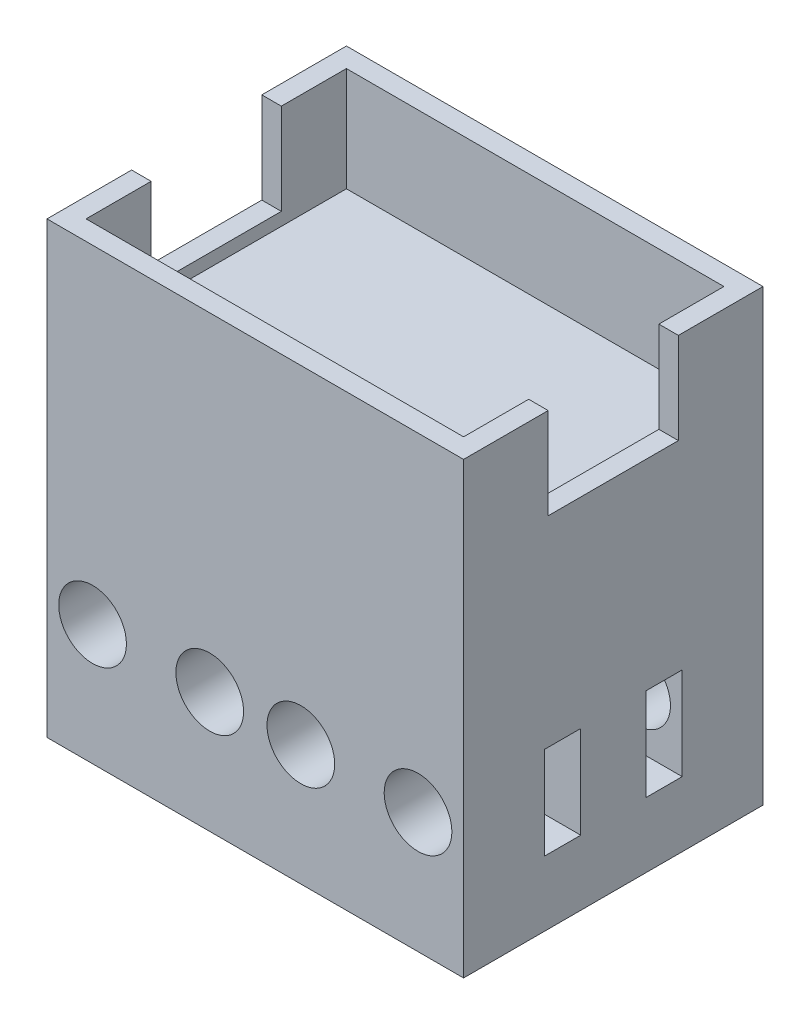
SolidWorks part; units mm, degrees
ref_plane "Front Plane" through (0, 0, 0) normal (0, 0, 1) x (1, 0, 0)
ref_plane "Top Plane" through (0, 0, 0) normal (0, 1, 0) x (1, 0, 0)
ref_plane "Right Plane" through (0, 0, 0) normal (1, 0, 0) x (0, 0, -1)
sketch "Sketch4" plane through (0, 0, 0) normal (0, 1, 0) x (1, 0, 0)
  line L1 (-16, -11.5) -> (16, -11.5)
  line L2 (-16, -11.5) -> (-16, 11.5)
  line L3 (-16, 11.5) -> (16, 11.5)
  line L4 (16, -11.5) -> (16, 11.5)
  line L5 (-16, -11.5) -> (16, 11.5) construction
  line L6 (-16, 11.5) -> (16, -11.5) construction
  point P0 (0, 0)
  dimension "D1" = 32
  dimension "D2" = 23
extrude "Boss-Extrude3" add sketch "Sketch4" along normal blind 19.5
sketch "Sketch5" plane through (0, 19.5, 0) normal (0, 1, 0) x (1, 0, 0)
  line L1 (-14.5, -10) -> (14.5, -10)
  line L2 (-14.5, -10) -> (-14.5, 10)
  line L3 (-14.5, 10) -> (14.5, 10)
  line L4 (14.5, -10) -> (14.5, 10)
  line L5 (-14.5, -10) -> (14.5, 10) construction
  line L6 (-14.5, 10) -> (14.5, -10) construction
  point P0 (0, 0)
  dimension "D1" = 29
  dimension "D2" = 20
extrude "Cut-Extrude2" cut sketch "Sketch5" against normal blind 8
sketch "Sketch7" plane through (16, 0, 0) normal (1, 0, 0) x (0, 0, -1)
  line L1 (-5, 12.5) -> (5, 12.5)
  line L2 (-5, 12.5) -> (-5, 19.5)
  line L3 (-5, 19.5) -> (5, 19.5)
  line L4 (5, 12.5) -> (5, 19.5)
  line L5 (-11.5, 19.5) -> (11.5, 19.5) construction
  point P6 (0, 19.5)
  point P8 (0, 19.5)
  dimension "D1" = 10
  dimension "D2" = 7
extrude "Cut-Extrude4" cut sketch "Sketch7" against normal through all
sketch "Sketch8" plane through (0, 0, 0) normal (0, -1, 0) x (-1, 0, 0)
  line L17 (-16, -11.5) -> (16, -11.5)
  line L18 (-16, -11.5) -> (-16, 11.5)
  line L19 (-16, 11.5) -> (16, 11.5)
  line L20 (16, -11.5) -> (16, 11.5)
  line L21 (-16, -11.5) -> (16, 11.5) construction
  line L22 (-16, 11.5) -> (16, -11.5) construction
  point P4 (0, 0)
extrude "Boss-Extrude4" add sketch "Sketch8" along normal blind 10
ref_plane "Plane1" through (0, 0, 0) normal (0, 0, -1) x (-1, 0, 0)
sketch "Sketch12" plane through (0, 0, -11.5) normal (0, 0, -1) x (-1, 0, 0)
  line L0 (0, 19.5) -> (0, -10) construction
  line L1 (-16, 19.5) -> (16, 19.5) construction
  line L2 (16, -10) -> (-16, -10) construction
  line L3 (-16, 19.5) -> (0, -10) construction
  line L4 (0, 19.5) -> (-16, -10) construction
  line L5 (-8, 4.75) -> (-8, -10) construction
  line L6 (-16, 19.5) -> (-16, -10) construction
  circle A0 centre (-12.5, -5.7269) radius 2.6
  circle A1 centre (-3.5, -5.7269) radius 2.6
  circle A2 centre (3.5, -5.7269) radius 2.6
  circle A3 centre (12.5, -5.7269) radius 2.6
  dimension "D1" = 5.2
  dimension "D3" = 3.5
  dimension "D2" = 4.2731
extrude "Cut-Extrude5" cut sketch "Sketch12" against normal blind 7
pattern_circular "CirPattern1" count 2 over 180 about axis through (0, 11.5, 0) along (0, 1, 0) of "Cut-Extrude5"
sketch "Sketch13" plane through (0, -10, 0) normal (0, -1, 0) x (-1, 0, 0)
  line L0 (16, -11.5) -> (16, 11.5) construction
  line L1 (16, 2.5) -> (1, 2.5)
  line L2 (16, 2.5) -> (16, 5.2916)
  line L3 (16, 5.2916) -> (1, 5.2916)
  line L4 (1, 2.5) -> (1, 5.2916)
  line L5 (16, 2.5) -> (1, 5.2916) construction
  line L6 (16, 5.2916) -> (1, 2.5) construction
  line L7 (13.475, 0) -> (-13.475, 0) construction
  line L8 (0, -11.5) -> (0, 11.5) construction
  line L9 (-16, -11.5) -> (16, -11.5) construction
  line L10 (16, 11.5) -> (-16, 11.5) construction
  line L11 (-16, 5.2916) -> (-1, 5.2916)
  line L12 (-1, 2.5) -> (-1, 5.2916)
  line L13 (-16, 2.5) -> (-1, 2.5)
  line L14 (-16, 2.5) -> (-16, 5.2916)
  line L15 (-16, -2.5) -> (-16, -5.2916)
  line L16 (-16, -2.5) -> (-1, -2.5)
  line L17 (-1, -2.5) -> (-1, -5.2916)
  line L18 (-16, -5.2916) -> (-1, -5.2916)
  line L19 (16, -5.2916) -> (1, -5.2916)
  line L20 (1, -2.5) -> (1, -5.2916)
  line L21 (16, -2.5) -> (1, -2.5)
  line L22 (16, -2.5) -> (16, -5.2916)
  point P4 (8.5, 3.8958)
  dimension "D1" = 15
  dimension "D2" = 2.7916
  dimension "D3" = 2.5
extrude "Cut-Extrude6" cut sketch "Sketch13" against normal blind 7.1
sketch "Sketch14" plane through (0, -10, 0) normal (0, -1, 0) x (-1, 0, 0)
  line L1 (16, 11.5) -> (-16, 11.5)
  line L2 (16, 11.5) -> (16, -11.5)
  line L3 (16, -11.5) -> (-16, -11.5)
  line L4 (-16, 11.5) -> (-16, -11.5)
  line L5 (16, 11.5) -> (-16, -11.5) construction
  line L6 (16, -11.5) -> (-16, 11.5) construction
  point P4 (0, 0)
extrude "Boss-Extrude5" add sketch "Sketch14" along normal blind 5
